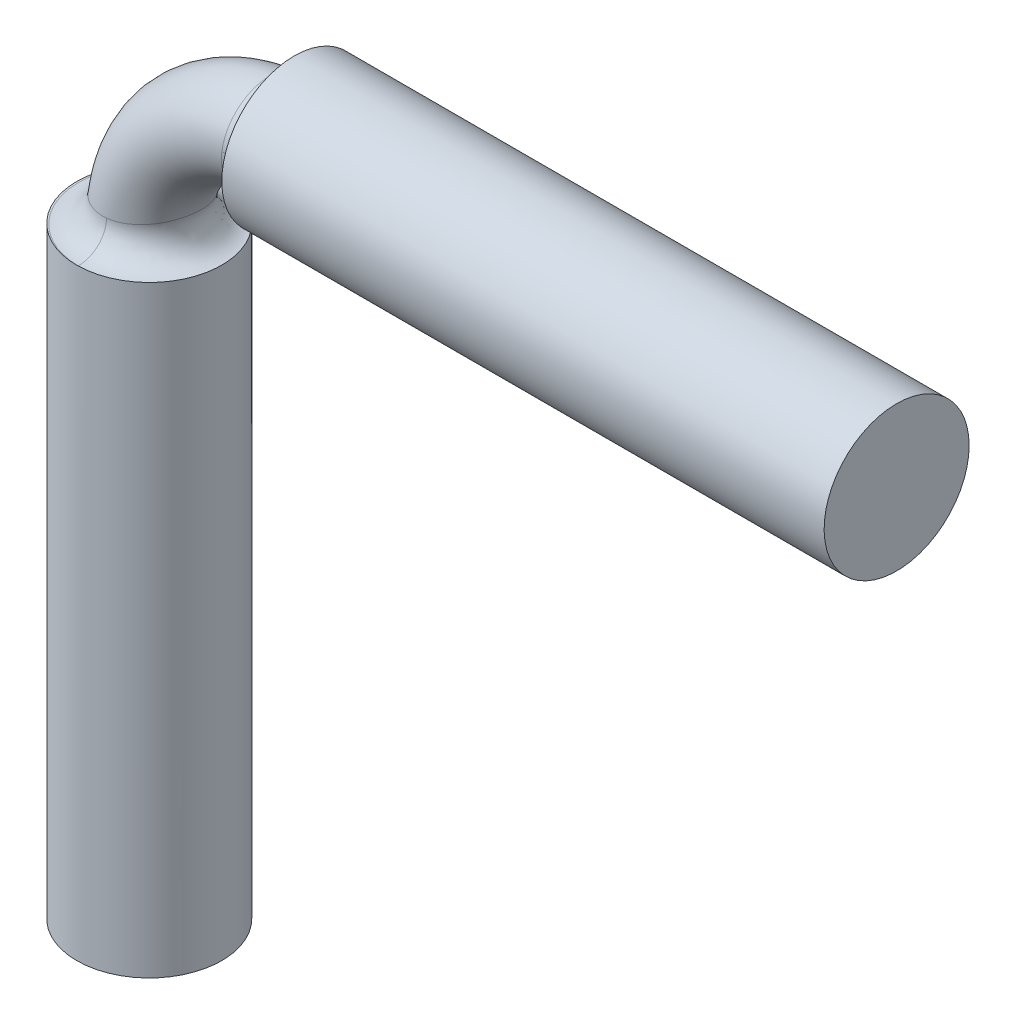
SolidWorks part; units mm, degrees
ref_plane "Ön Düzlem" through (0, 0, 0) normal (0, 0, 1) x (1, 0, 0)
ref_plane "Üst Düzlem" through (0, 0, 0) normal (0, 1, 0) x (1, 0, 0)
ref_plane "Sağ Düzlem" through (0, 0, 0) normal (1, 0, 0) x (0, 0, -1)
sketch "Çizim1" plane through (0, 0, 0) normal (0, 1, 0) x (1, 0, 0)
  circle A0 centre (0, 0) radius 3.25
  dimension "D1" = 6.5
extrude "Yükseklik-Ekstrüzyon1" add sketch "Çizim1" along normal blind 27
sketch "Çizim2" plane through (0, 0, 0) normal (0, 0, 1) x (1, 0, 0)
  line L0 (0, 27) -> (0, 0) construction
  line L1 (3.25, 27) -> (-3.25, 27) construction
  line L2 (6.5, 33.5) -> (17.9394, 33.5) construction
  arc A0 (6.5, 33.5) -> (0, 27) centre (6.5, 27) ccw
  dimension "D1" = 13
sketch "Çizim3" plane through (0, 27, 0) normal (0, 1, 0) x (1, 0, 0)
  circle A0 centre (0, 0) radius 2
  dimension "D1" = 4
sweep "Süpür1" add profiles "Çizim3" path "Çizim2"
sketch "Çizim4" plane through (6.5, 0, 0) normal (1, 0, 0) x (0, 0, -1)
  circle A0 centre (0, 33.5) radius 3.25
  circle A1 centre (0, 33.5) radius 2 construction
  dimension "D1" = 6.5
extrude "Yükseklik-Ekstrüzyon2" add sketch "Çizim4" along normal blind 27
fillet "Radyus1" radius 1.25 2 edges at (0, 27, 2) (6.5, 33.5, 2)
